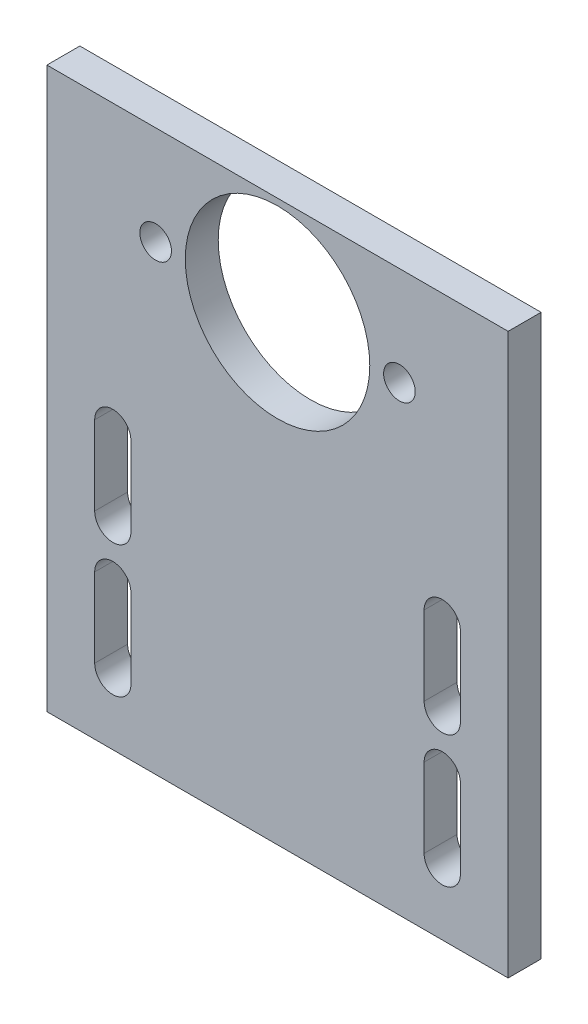
SolidWorks part; units mm, degrees
ref_plane "Front Plane" through (0, 0, 0) normal (0, 0, 1) x (1, 0, 0)
ref_plane "Top Plane" through (0, 0, 0) normal (0, 1, 0) x (1, 0, 0)
ref_plane "Right Plane" through (0, 0, 0) normal (1, 0, 0) x (0, 0, -1)
sketch "Sketch1" plane through (0, 0, 0) normal (0, 0, 1) x (1, 0, 0)
  line L0 (0, 0) -> (0, 100) construction
  line L1 (-35, -15) -> (35, -15) construction
  line L2 (-35, -15) -> (-35, 100)
  line L3 (-35, 100) -> (35, 100)
  line L4 (35, -15) -> (35, 100)
  line L5 (-35, -15) -> (35, 100) construction
  line L6 (-35, 100) -> (35, -15) construction
  line L7 (-18.5, 35) -> (18.5, 35) construction
  line L8 (0, 0) -> (0, -15) construction
  line L9 (-25, -5) -> (25, -5) construction
  line L10 (-35, -15) -> (-35, -35)
  line L11 (-25, -5) -> (-25, 7) construction
  line L12 (-35, -35) -> (35, -35)
  line L13 (35, -35) -> (35, -15)
  line L14 (-27.75, -5) -> (-27.75, 7)
  line L15 (-22.25, -5) -> (-22.25, 7)
  line L16 (25, -5) -> (25, 7) construction
  line L17 (27.75, -5) -> (27.75, 7)
  line L18 (22.25, -5) -> (22.25, 7)
  line L19 (-25, -25) -> (-25, -13) construction
  line L20 (-27.75, -25) -> (-27.75, -13)
  line L21 (-22.25, -25) -> (-22.25, -13)
  line L22 (25, -25) -> (25, -13) construction
  line L23 (27.75, -25) -> (27.75, -13)
  line L24 (22.25, -25) -> (22.25, -13)
  line L25 (-35, 50) -> (35, 50)
  circle A0 centre (-18.5, 35) radius 2.4
  circle A1 centre (18.5, 35) radius 2.4
  circle A2 centre (0, 35) radius 5
  circle A3 centre (-25, -5) radius 2.75 construction
  circle A4 centre (25, -5) radius 2.75 construction
  circle A5 centre (25, -25) radius 2.75 construction
  circle A6 centre (-25, -25) radius 2.75 construction
  circle A7 centre (0, 35) radius 14
  arc A8 (-27.75, -5) -> (-22.25, -5) centre (-25, -5) ccw
  arc A9 (-22.25, 7) -> (-27.75, 7) centre (-25, 7) ccw
  arc A10 (27.75, -5) -> (22.25, -5) centre (25, -5) cw
  arc A11 (22.25, 7) -> (27.75, 7) centre (25, 7) cw
  circle A12 centre (25, -5) radius 2.75 construction
  arc A13 (-27.75, -25) -> (-22.25, -25) centre (-25, -25) ccw
  arc A14 (-22.25, -13) -> (-27.75, -13) centre (-25, -13) ccw
  arc A15 (27.75, -25) -> (22.25, -25) centre (25, -25) cw
  arc A16 (22.25, -13) -> (27.75, -13) centre (25, -13) cw
  circle A17 centre (25, -25) radius 2.75 construction
  point P0 (0, 42.5)
  point P5 (-25, 1)
  point P10 (0, 35)
  point P18 (0, -5)
  point P34 (25, 1)
  point P41 (-25, -19)
  point P48 (25, -19)
  dimension "D4" = 4.8
  dimension "D5" = 10
  dimension "D6" = 5.5
  dimension "D11" = 28
  dimension "D14" = 2.75
  dimension "D15" = 2.75
  dimension "D1" = 70
  dimension "D2" = 115
  dimension "D3" = 37
  dimension "D7" = 10
  dimension "D8" = 65
  dimension "D9" = 10
  dimension "D10" = 20
  dimension "D12" = 10
  dimension "D13" = 12
  dimension "D16" = 12
  dimension "D17" = 50
extrude "Boss-Extrude1" add sketch "Sketch1" along normal blind 5 contours L25 L2 L10 L12 L13 L4 A14 L21 A13 L20 A9 L15 A8 L14 A7 A1 A0 L18 A11 L17 A10 L24 A16 L23 A15 region at (0, 5.0695, 0)
